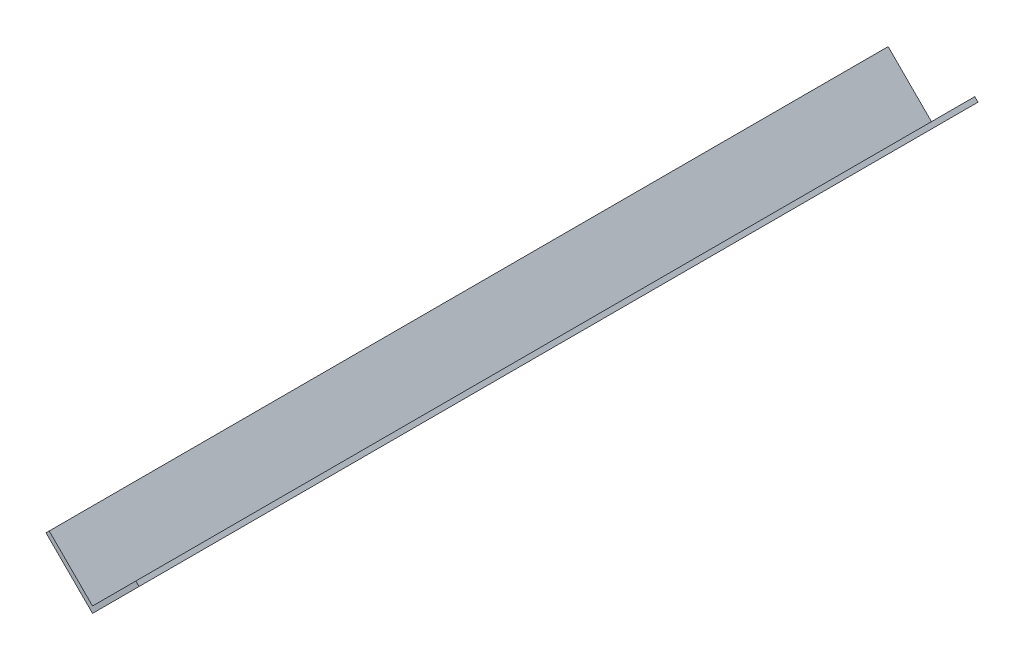
SolidWorks part; units mm, degrees
material "6061 Alloy"
ref_plane "Front Plane" through (0, 0, 0) normal (0, 0, 1) x (1, 0, 0)
ref_plane "Top Plane" through (0, 0, 0) normal (0, 1, 0) x (1, 0, 0)
ref_plane "Right Plane" through (0, 0, 0) normal (1, 0, 0) x (0, 0, -1)
sketch "Sketch1" plane through (0, 0, 0) normal (0, 0, 1) x (1, 0, 0)
  line L0 (0, 0) -> (-17.9605, 17.9605)
  line L1 (-17.9605, 17.9605) -> (-16.7257, 19.1953)
  line L2 (-16.7257, 19.1953) -> (0, 2.4696)
  line L3 (0, 2.4696) -> (16.7257, 19.1953)
  line L4 (16.7257, 19.1953) -> (17.9605, 17.9605)
  line L5 (17.9605, 17.9605) -> (0, 0)
  dimension "D1" = 1.7463
  dimension "D2" = 25.4
extrude "Boss-Extrude1" add sketch "Sketch1" along normal blind 323.85
sketch "Sketch3" [suppressed] plane through (0, 0, 0) normal (1, 0, 0) x (0, 0, -1)
  line L5 (-323.85, 0) -> (-323.85, 17.9605) construction
  line L6 (-209.55, 19.1953) -> (-215.9, 19.1953)
  line L7 (-215.9, 19.1953) -> (-215.9, 16.0203)
  line L8 (-209.55, 16.0203) -> (-209.55, 19.1953)
  line L9 (-107.95, 19.1953) -> (-114.3, 19.1953)
  line L10 (-114.3, 19.1953) -> (-114.3, 16.0203)
  line L11 (-107.95, 16.0203) -> (-107.95, 19.1953)
  line L16 (-6.35, 19.1953) -> (-12.7, 19.1953)
  line L17 (-12.7, 19.1953) -> (-12.7, 16.0203)
  line L22 (-6.35, 16.0203) -> (-6.35, 19.1953)
  line L23 (0, 0) -> (0, 17.9605) construction
  line L30 (-317.5, 19.1953) -> (-317.5, 16.0203)
  line L31 (-323.85, 19.1953) -> (0, 19.1953) construction
  line L32 (-311.15, 16.0203) -> (-311.15, 19.1953)
  line L33 (-311.15, 19.1953) -> (-317.5, 19.1953)
  arc A0 (-317.5, 16.0203) -> (-311.15, 16.0203) centre (-314.325, 16.0203) ccw
  arc A1 (-215.9, 16.0203) -> (-209.55, 16.0203) centre (-212.725, 16.0203) ccw
  arc A2 (-114.3, 16.0203) -> (-107.95, 16.0203) centre (-111.125, 16.0203) ccw
  arc A3 (-12.7, 16.0203) -> (-6.35, 16.0203) centre (-9.525, 16.0203) ccw
  dimension "D1" = 9.525
  dimension "D5" = 3.175
  dimension "D2" = 4
  dimension "D3" = 9.525
  dimension "D4" = 6.35
extrude "Cut-Extrude2" [suppressed] cut sketch "Sketch3" against normal through all both and the other way through all
sketch "Sketch4" [suppressed] plane through (0, 0, 0) normal (0.7071, -0.7071, 0) x (0, 0, -1)
  line L0 (-317.5, 25.4) -> (-317.5, 19.5947)
  line L1 (-311.15, 19.5947) -> (-311.15, 25.4)
  line L2 (-215.9, 25.4) -> (-215.9, 19.5947)
  line L3 (-209.55, 19.5947) -> (-209.55, 25.4)
  line L4 (-311.15, 25.4) -> (-215.9, 25.4) construction
  line L5 (-215.9, 22.6561) -> (-215.9, 25.4) construction
  line L6 (-114.3, 25.4) -> (-114.3, 19.5947)
  line L7 (-107.95, 19.5947) -> (-107.95, 25.4)
  line L8 (-12.7, 25.4) -> (-12.7, 19.5947)
  line L9 (-6.35, 19.5947) -> (-6.35, 25.4)
  line L10 (-209.55, 25.4) -> (-209.55, 22.6561) construction
  line L11 (-114.3, 22.6561) -> (-114.3, 25.4) construction
  line L12 (-107.95, 25.4) -> (-107.95, 22.6561) construction
  line L13 (-209.55, 25.4) -> (-114.3, 25.4) construction
  line L14 (-6.35, 25.4) -> (-6.35, 22.6561) construction
  line L15 (-12.7, 22.6561) -> (-12.7, 25.4) construction
  line L16 (-107.95, 25.4) -> (-12.7, 25.4) construction
  line L17 (-311.15, 25.4) -> (-317.5, 25.4)
  line L18 (-209.55, 25.4) -> (-215.9, 25.4)
  line L19 (-107.95, 25.4) -> (-114.3, 25.4)
  line L20 (-6.35, 25.4) -> (-12.7, 25.4)
  arc A0 (-317.5, 19.5947) -> (-311.15, 19.5947) centre (-314.325, 19.5947) ccw
  arc A1 (-215.9, 19.5947) -> (-209.55, 19.5947) centre (-212.725, 19.5947) ccw
  arc A3 (-114.3, 19.5947) -> (-107.95, 19.5947) centre (-111.125, 19.5947) ccw
  arc A4 (-12.7, 19.5947) -> (-6.35, 19.5947) centre (-9.525, 19.5947) ccw
  ellipse E1 centre (-9.525, 20.9099) end of major axis (-9.525, 25.4) minor radius 3.175 (-12.7, 20.9099) -> (-6.35, 20.9099) ccw construction
  ellipse E2 centre (-212.725, 20.9099) end of major axis (-212.725, 25.4) minor radius 3.175 (-215.9, 20.9099) -> (-209.55, 20.9099) ccw construction
  ellipse E4 centre (-314.325, 20.9099) end of major axis (-314.325, 25.4) minor radius 3.175 (-317.5, 20.9099) -> (-311.15, 20.9099) ccw construction
  ellipse E5 centre (-111.125, 20.9099) end of major axis (-111.125, 25.4) minor radius 3.175 (-114.3, 20.9099) -> (-107.95, 20.9099) ccw construction
extrude "Cut-Extrude3" [suppressed] cut sketch "Sketch4" against normal through all both and the other way through all
mirror "Mirror1" [suppressed] about plane through (0, 0, 0) normal (1, 0, 0)
